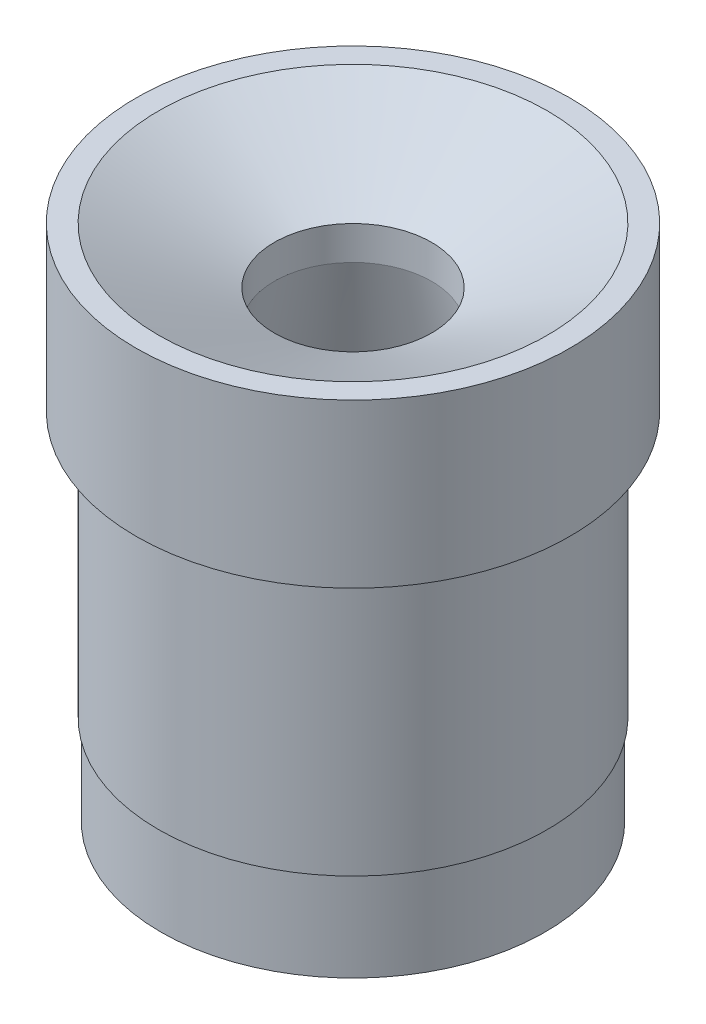
SolidWorks part; units mm, degrees
ref_plane "Front Plane" through (0, 0, 0) normal (0, 0, 1) x (1, 0, 0)
ref_plane "Top Plane" through (0, 0, 0) normal (0, 1, 0) x (1, 0, 0)
ref_plane "Right Plane" through (0, 0, 0) normal (1, 0, 0) x (0, 0, -1)
sketch "Sketch1" plane through (0, 0, 0) normal (0, 1, 0) x (1, 0, 0)
  circle A0 centre (0, 0) radius 24.511
  dimension "D1" = 49.022
extrude "Boss-Extrude1" [suppressed] add sketch "Sketch1" along normal blind 18.415
sketch "Sketch2" [suppressed] plane through (0, 0, 0) normal (0, -1, 0) x (1, 0, 0)
  circle A0 centre (0, 0) radius 21.463
  dimension "D1" = 42.926
extrude "Boss-Extrude2" [suppressed] add sketch "Sketch2" along normal blind 44.45
ref_axis "Axis1" [suppressed] through (0, -44.45, 0) along (0, 1, 0)
sketch "Sketch4" plane through (0, 0, 0) normal (1, 0, 0) x (0, 0, -1)
  line L0 (24.511, 0) -> (24.511, 18.415)
  line L1 (24.511, 0) -> (21.971, 0)
  line L3 (21.717, -40.132) -> (20.066, -40.132)
  line L4 (20.066, -40.132) -> (8.89, 8.2766)
  line L5 (8.89, 8.2766) -> (8.89, 12.0866)
  line L6 (8.89, 12.0866) -> (21.971, 18.415)
  line L7 (21.971, 18.415) -> (24.511, 18.415)
  line L8 (21.717, -40.132) -> (21.717, -29.972)
  line L9 (21.717, -29.972) -> (21.971, -29.972)
  line L10 (21.971, -29.972) -> (21.971, 0)
  point P3 (0, 0)
  dimension "D1" = 18.415
  dimension "D2" = 21.717
  dimension "D3" = 3.81
  dimension "D4" = 8.89
  dimension "D5" = 21.971
  dimension "D6" = 24.511
  dimension "D7" = 13
  dimension "D8" = 20.066
  dimension "D9" = 10.16
  dimension "D10" = 40.132
ref_axis "Axis2" through (0, 21.5582, 0) along (0, -1, 0)
revolve "Revolve1" add sketch "Sketch4" angle 360 about axis through (0, 21.5582, 0) along (0, -1, 0)
